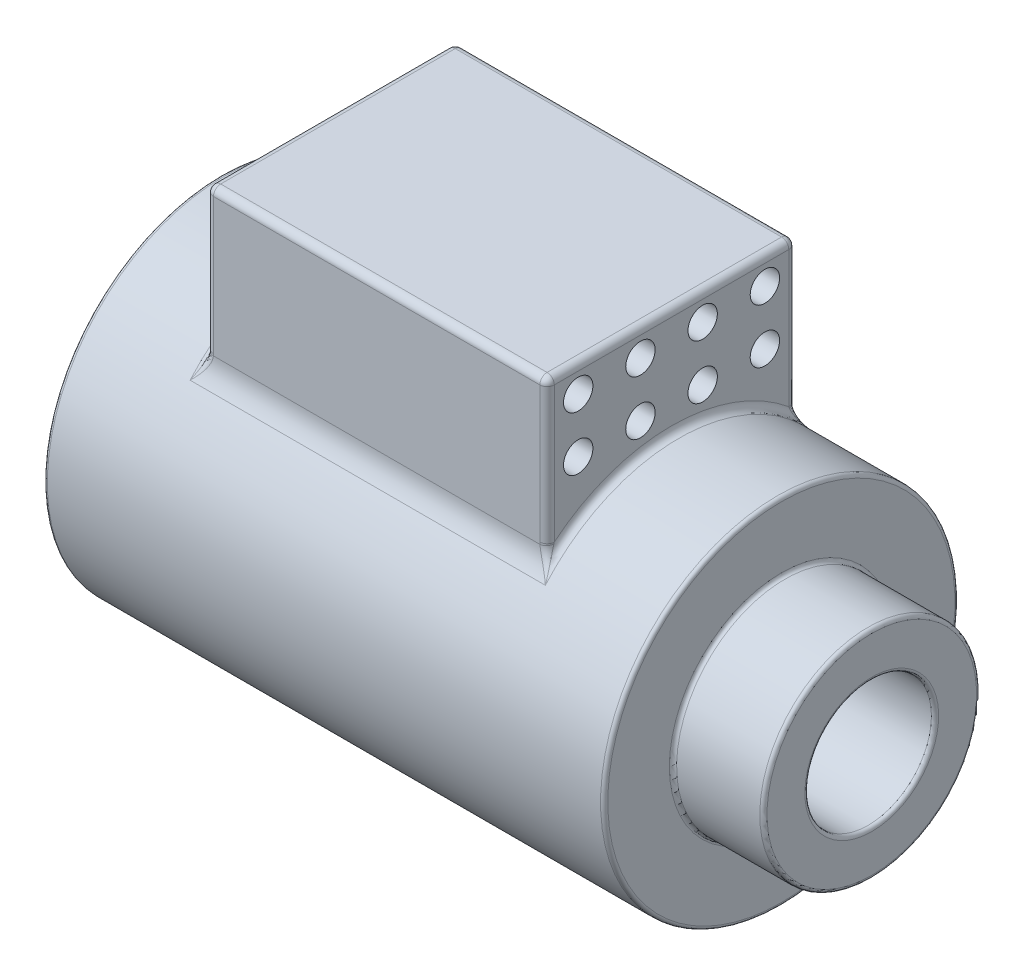
SolidWorks part; units mm, degrees
material "Custom PLA"
ref_plane "Front Plane" through (0, 0, 0) normal (0, 0, 1) x (1, 0, 0)
ref_plane "Top Plane" through (0, 0, 0) normal (0, 1, 0) x (1, 0, 0)
ref_plane "Right Plane" through (0, 0, 0) normal (1, 0, 0) x (0, 0, -1)
sketch "Sketch2" plane through (0, 0, 0) normal (0, 0, 1) x (1, 0, 0)
  line L1 (89.65, 0) -> (-89.65, 0)
  line L2 (89.65, 0) -> (89.65, 49)
  line L3 (89.65, 49) -> (-89.65, 49)
  line L4 (-89.65, 0) -> (-89.65, 49)
  point P4 (0, 0)
  dimension "D1" = 179.3
  dimension "D2" = 49
revolve "Revolve1" [suppressed] add sketch "Sketch2" angle 360 about L1
sketch "Sketch3" [suppressed] plane through (89.65, 0, 0) normal (1, 0, 0) x (0, 0, -1)
  circle A0 centre (0, 0) radius 15
  dimension "D1" = 30
extrude "Cut-Extrude1" [suppressed] cut sketch "Sketch3" against normal blind 210
sketch "Sketch4" plane through (0, 0, 0) normal (0, 0, 1) x (1, 0, 0)
  line L0 (-90, 0) -> (90, 0)
  line L1 (90, 0) -> (90, 29.975)
  line L2 (90, 29.975) -> (65, 29.975)
  line L3 (65, 29.975) -> (65, 49)
  line L4 (65, 49) -> (-90, 49)
  line L5 (-90, 49) -> (-90, 0)
  point P3 (0, 0)
  dimension "D1" = 155
  dimension "D2" = 25
  dimension "D3" = 29.975
  dimension "D4" = 49
revolve "Revolve2" add sketch "Sketch4" angle 360 about L0
sketch "Sketch5" plane through (90, 0, 0) normal (1, 0, 0) x (0, 0, -1)
  circle A0 centre (0, 0) radius 17.5
  dimension "D1" = 35
extrude "Cut-Extrude2" cut sketch "Sketch5" against normal blind 177
ref_plane "Plane1" through (0, 49, 0) normal (0, 1, 0) x (1, 0, 0)
sketch "Sketch6" plane through (0, 49, 0) normal (0, 1, 0) x (1, 0, 0)
  line L1 (-59.625, 34.425) -> (34.625, 34.425)
  line L2 (-59.625, 34.425) -> (-59.625, -34.425)
  line L3 (-59.625, -34.425) -> (34.625, -34.425)
  line L4 (34.625, 34.425) -> (34.625, -34.425)
  line L6 (-90, 0) -> (65, 0) construction
  line L7 (-90, 49) -> (-90, -49) construction
  line L8 (65, -49) -> (65, 49) construction
  line L9 (-12.5, 63.5465) -> (-12.5, -66.4968) construction
  point P4 (-12.5, -34.425)
  point P5 (-59.625, 0)
  dimension "D1" = 77.5
  dimension "D2" = 94.25
  dimension "D3" = 68.85
extrude "Boss-Extrude1" add sketch "Sketch6" along normal blind 30 and the other way up to surface other way up to face at (-90, -49, 0)
fillet "Fillet2" [suppressed] radius 30
ref_plane "Plane2" through (14.625, 0, 0) normal (1, 0, 0) x (0, 0, -1)
ref_plane "Plane3" through (-59.625, 0, 0) normal (-1, 0, 0) x (0, 0, 1)
sketch "Sketch7" plane through (14.625, 0, 0) normal (1, 0, 0) x (0, 0, -1)
  line L1 (-40, 196) -> (40, 196)
  line L2 (-40, 196) -> (-40, 166)
  line L3 (-40, 166) -> (40, 166)
  line L4 (40, 196) -> (40, 166)
  line L5 (0, 34.5583) -> (0, 302.6635) construction
  point P9 (0, 196)
  dimension "D1" = 80
  dimension "D2" = 30
  dimension "D3" = 166
ref_plane "Plane4" through (36.625, 0, 0) normal (1, 0, 0) x (0, 0, -1)
ref_plane "Plane5" through (0, 250, 0) normal (0, 1, 0) x (1, 0, 0)
sketch "Sketch8" plane through (0, 250, 0) normal (0, 1, 0) x (1, 0, 0)
  line L0 (36.625, -85.597) -> (36.625, 85.597) construction
  line L1 (36.625, 40) -> (66.625, 40)
  line L2 (36.625, 40) -> (36.625, -40)
  line L3 (36.625, -40) -> (66.625, -40)
  line L4 (66.625, 40) -> (66.625, -40)
  line L5 (-101.8526, 0) -> (154.8726, 0) construction
  point P9 (36.625, 0)
  dimension "D1" = 30
  dimension "D2" = 80
loft "Loft1" [suppressed] add profiles "Sketch7", "Sketch8" start constraint normal to profile start tangent length 1.4
sketch "Sketch9" plane through (36.625, 0, 0) normal (1, 0, 0) x (0, 0, -1)
  line L1 (-40, 196.0467) -> (40, 196.0467)
  line L2 (-40, 196.0467) -> (-40, 166)
  line L3 (-40, 166) -> (40, 166)
  line L4 (40, 196.0467) -> (40, 166)
extrude "Boss-Extrude2" [suppressed] add sketch "Sketch9" against normal blind 20
sketch "Sketch10" [suppressed] plane through (36.625, 0, 0) normal (1, 0, 0) x (0, 0, -1)
  line L0 (-50, 250) -> (-50, 300)
  line L3 (50, 250) -> (50, 300)
  line L4 (-50, 250) -> (50, 250)
  line L5 (-50, 300) -> (50, 300) construction
  line L6 (0, 0) -> (0, 363.1332) construction
  line L8 (53.9, 250) -> (-53.9, 250) construction
  arc A0 (-50, 300) -> (50, 300) centre (0, 300) cw
  point P3 (0, 250)
  dimension "D2" = 50
  dimension "D1" = 100
ref_plane "Plane6" through (-12.5, 0, 0) normal (1, 0, 0) x (0, 0, -1)
ref_plane "Plane7" through (0, 0, 0) normal (0, 0, 1) x (1, 0, 0)
ref_plane "Plane8" through (0, 49, 0) normal (0, 1, 0) x (1, 0, 0)
sketch "Sketch11" plane through (-87, 0, 0) normal (1, 0, 0) x (0, 0, -1)
  line L0 (0, 17.5) -> (0, -12) construction
  circle A0 centre (0, 0) radius 12 construction
  circle A1 centre (0, 0) radius 17.5 construction
  circle A2 centre (0, 12) radius 2.3
  dimension "D1" = 24
  dimension "D2" = 4.6
extrude "Cut-Extrude3" cut sketch "Sketch11" against normal up to next
pattern_circular "CirPattern1" count 6 over 360 about axis through (-87, 0, 0) along (1, 0, 0) of "Cut-Extrude3"
sketch "Sketch12" plane through (-87, 0, 0) normal (1, 0, 0) x (0, 0, -1)
  circle A0 centre (0, 12) radius 2.3 construction
  circle A1 centre (0, 0) radius 17.5 construction
  circle A2 centre (0, 0) radius 17.5 construction
  point P0 (0, 14.3)
  point P1 (0, 17.5)
sketch "Sketch13" plane through (-59.625, 0, 0) normal (-1, 0, 0) x (0, 0, 1)
  line L0 (0, 79) -> (0, 49) construction
  line L1 (-34.425, 79) -> (34.425, 79) construction
  line L2 (-34.425, 64) -> (34.425, 64) construction
  line L3 (-34.425, 79) -> (-34.425, 34.87) construction
  line L4 (34.425, 79) -> (34.425, 34.87) construction
  line L5 (-34.425, 71.5) -> (34.425, 71.5) construction
  line L6 (-17.2125, 79) -> (-17.2125, 49) construction
  line L7 (53.9, 49) -> (-53.9, 49) construction
  line L8 (-34.425, 56.5) -> (34.425, 56.5) construction
  line L9 (-25.8187, 79) -> (-25.8187, 49) construction
  circle A0 centre (0, 0) radius 49 construction
  circle A2 centre (-25.8187, 71.5) radius 4.065
  dimension "D5" = 8.6062
  dimension "D6" = 8.13
  dimension "D1" = 15
  dimension "D2" = 7.5
  dimension "D3" = 17.2125
  dimension "D4" = 22.5
extrude "Cut-Extrude4" cut sketch "Sketch13" against normal blind 6.73
pattern_linear "LPattern1" count 4 spacing 17.21 along (0, 0, 1) count 2 spacing 15 along (0, -1, 0) of "Cut-Extrude4"
mirror "Mirror1" about plane through (-12.5, 0, 0) normal (1, 0, 0) of "LPattern1"
fillet "Fillet3" radius 1 5 edges at (65, -29.975, 0) (65, -49, 0) (90, -29.975, 0) (90, 0, -17.5) (-90, -49, 0)
fillet "Fillet4" radius 10 2 edges at (-12.5, 34.87, 34.425) (-12.5, 34.87, -34.425)
fillet "Fillet5" radius 2 2 edges at (-59.625, 49, 0) (34.625, 49, 0)
fillet "Fillet6" radius 2 16 edges at (-12.5, 79, -34.425) (34.625, 79, 0) (-12.5, 79, 34.425) (-59.625, 79, 0) (34.8672, 35.908, 34.86) (34.625, 38.1886, 34.4453) (-59.8672, 35.908, 34.86) (-59.625, 38.1886, 34.4453) (-59.8672, 35.908, -34.86) (-59.625, 38.1886, -34.4453) (34.8672, 35.908, -34.86) (34.625, 38.1886, -34.4453) (34.625, 58.9127, 34.425) (-59.625, 58.9127, 34.425) (-59.625, 58.9127, -34.425) (34.625, 58.9127, -34.425)
